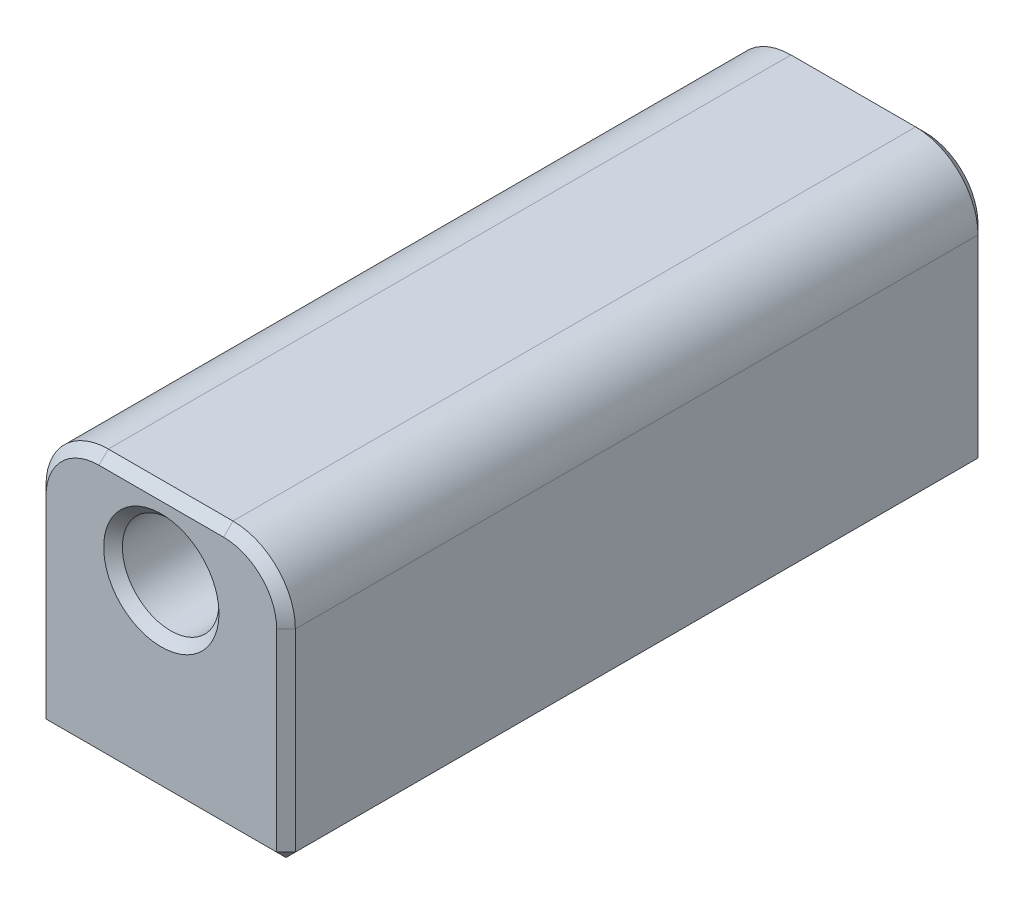
SolidWorks part; units mm, degrees
ref_plane "Front Plane" through (0, 0, 0) normal (0, 0, 1) x (1, 0, 0)
ref_plane "Top Plane" through (0, 0, 0) normal (0, 1, 0) x (1, 0, 0)
ref_plane "Right Plane" through (0, 0, 0) normal (1, 0, 0) x (0, 0, -1)
sketch "Sketch1" plane through (0, 0, 0) normal (0, 1, 0) x (1, 0, 0)
  line L0 (0, -6.35) -> (0, 6.35) construction
  line L1 (5.08, -14.2875) -> (-5.08, -14.2875)
  line L2 (5.08, -14.2875) -> (5.08, 14.2875)
  line L3 (5.08, 14.2875) -> (-5.08, 14.2875)
  line L4 (-5.08, -14.2875) -> (-5.08, 14.2875)
  line L5 (5.08, -14.2875) -> (-5.08, 14.2875) construction
  line L6 (5.08, 14.2875) -> (-5.08, -14.2875) construction
  circle A0 centre (0, 6.35) radius 2.032
  circle A1 centre (0, -6.35) radius 2.032
  point P0 (0, 0)
  point P9 (0, 0)
  dimension "D4" = 4.064
  dimension "D1" = 28.575
  dimension "D2" = 10.16
  dimension "D3" = 12.7
extrude "Boss-Extrude1" add sketch "Sketch1" along normal blind 10.795 contours A1 | A0 | L4 L1 L2 L3 A1 A0 region at (0, 0, 0) region at (0, 0, -6.35) region at (0, 0, 6.35)
extrude "Cut-Extrude3" cut sketch "Sketch1<6>" along normal blind 5.08 contours A1 | A0 region at (0, 0, -6.35) region at (0, 0, 6.35)
sketch "Sketch1<6>" plane through (0, 0, 0) normal (0, 1, 0) x (1, 0, 0) same geometry as "Sketch1"
sketch "Sketch3" plane through (0, 0, 14.2875) normal (0, 0, 1) x (1, 0, 0)
  line L0 (-5.08, 10.795) -> (-5.08, 0) construction
  circle A0 centre (0, 7.62) radius 1.9685
  dimension "D1" = 3.937
  dimension "D2" = 7.62
  dimension "D3" = 5.08
extrude "Cut-Extrude4" cut sketch "Sketch3" against normal through all
fillet "Fillet1" radius 2.54 2 edges at (5.08, 10.795, 0) (-5.08, 10.795, 0)
chamfer "Chamfer2" distance 0.381 angle 45 18 edges at (-5.08, 4.1275, -14.2875) (5.08, 4.1275, -14.2875) (-5.08, 4.1275, 14.2875) (5.08, 4.1275, 14.2875) (-4.3361, 10.0511, -14.2875) (0, 10.795, -14.2875) (4.3361, 10.0511, -14.2875) (-4.3361, 10.0511, 14.2875) (0, 10.795, 14.2875) (4.3361, 10.0511, 14.2875) (0, 0, -4.318) (0, 0, 8.382) (1.9685, 7.62, 14.2875) (1.9685, 7.62, -14.2875) (0, 0, 14.2875) (-5.08, 0, 0) (0, 0, -14.2875) (5.08, 0, 0)
